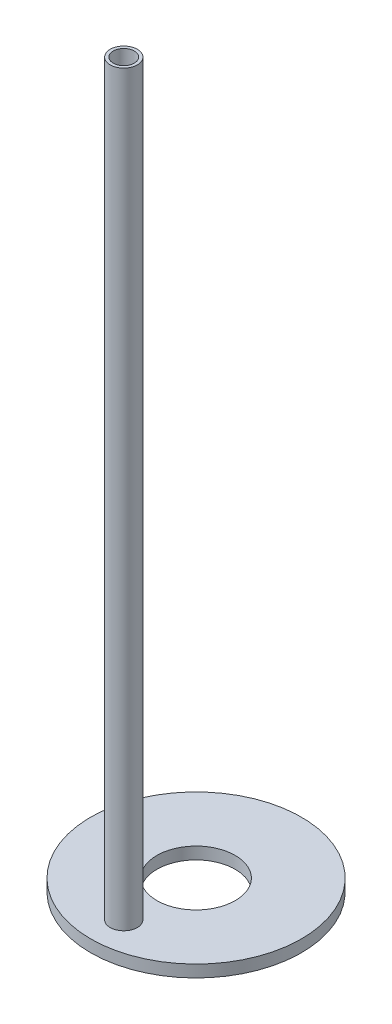
SolidWorks part; units mm, degrees
ref_plane "Front Plane" through (0, 0, 0) normal (0, 0, 1) x (1, 0, 0)
ref_plane "Top Plane" through (0, 0, 0) normal (0, 1, 0) x (1, 0, 0)
ref_plane "Right Plane" through (0, 0, 0) normal (1, 0, 0) x (0, 0, -1)
sketch "Sketch2" plane through (0, 0, 0) normal (0, 1, 0) x (1, 0, 0)
  line L0 (0, 1) -> (0, -1) construction
  line L1 (0, 0) -> (0, -12) construction
  circle A0 centre (0, 0) radius 17.5
  circle A2 centre (0, 0) radius 6.5
  circle A3 centre (0, -12) radius 2.25
  point P8 (0, 0)
  dimension "D1" = 35
  dimension "D2" = 13
  dimension "D3" = 12
  dimension "D6" = 4.5
  dimension "D4" = 2
extrude "Plate" add sketch "Sketch2" along normal mid plane 2 contours A0 A3 | A3 region at (-17.005, 0, 0) region at (0, 0, 12)
extrude "Rod" add sketch "Sketch2<4>" along normal blind 125 contours A3
sketch "Sketch2<4>" plane through (0, 0, 0) normal (0, 1, 0) x (1, 0, 0) same geometry as "Sketch2"
sketch "Sketch3" plane through (0, 125, 0) normal (0, 1, 0) x (1, 0, 0)
  circle A0 centre (0, -12) radius 1.75
  dimension "D1" = 3.5
extrude "Cut-Extrude1" cut sketch "Sketch3" against normal through all
